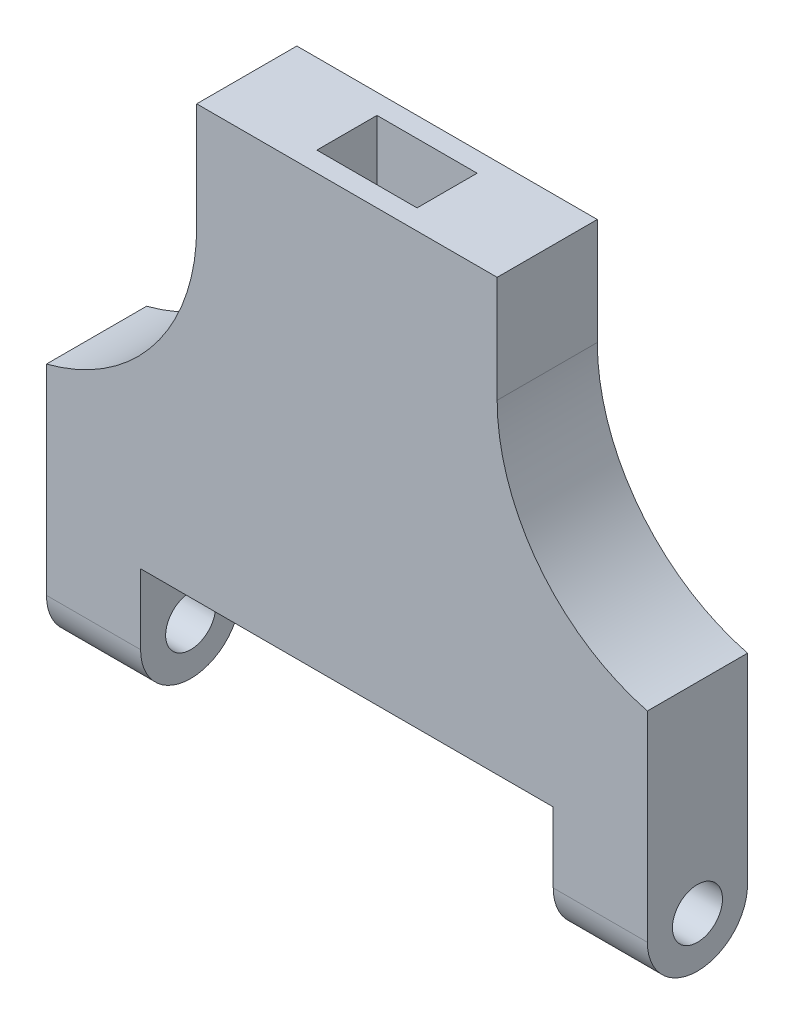
SolidWorks part; units mm, degrees
ref_plane "Front" through (0, 0, 0) normal (0, 0, 1) x (1, 0, 0)
ref_plane "Top" through (0, 0, 0) normal (0, 1, 0) x (1, 0, 0)
ref_plane "Right" through (0, 0, 0) normal (1, 0, 0) x (0, 0, -1)
sketch "Sketch1" plane through (0, 0, 0) normal (0, 0, 1) x (1, 0, 0)
  line L1 (0, 0) -> (20, 0)
  line L2 (0, 0) -> (0, 60)
  line L3 (0, 60) -> (20, 60)
  line L4 (20, 0) -> (20, 60)
  dimension "D1" = 60
  dimension "D2" = 20
extrude "Boss-Extrude1" add sketch "Sketch1" along normal blind 5
sketch "Sketch2" plane through (20, 0, 0) normal (1, 0, 0) x (0, 0, -1)
  line L0 (-5, 60) -> (0, 60) construction
  circle A0 centre (-2.5, 60) radius 2.5
  circle A1 centre (-2.5, 60) radius 1.25
  dimension "D1" = 2.5
extrude "Boss-Extrude2" add sketch "Sketch2" against normal up to surface (20 mm away) up to face at (0, 30, 2.5)
sketch "Sketch3" plane through (0, 0, 0) normal (-1, 0, 0) x (0, 0, 1)
  line L0 (3.75, 60) -> (1.25, 60) construction
  circle A0 centre (2.5, 60) radius 1.25
extrude "Cut-Extrude1" cut sketch "Sketch3" against normal blind 29
sketch "Sketch4" plane through (0, 0, 0) normal (-1, 0, 0) x (0, 0, 1)
  line L0 (5, 0) -> (0, 0) construction
  circle A0 centre (2.5, 0) radius 2.5
  circle A1 centre (2.5, 0) radius 1.25
  dimension "D1" = 2.5
extrude "Boss-Extrude3" add sketch "Sketch4" against normal up to surface (20 mm away) up to face at (20, 30.625, 2.5)
sketch "Sketch5" plane through (20, 0, 0) normal (1, 0, 0) x (0, 0, -1)
  line L0 (-3.75, 0) -> (-1.25, 0) construction
  circle A0 centre (-2.5, 0) radius 1.25
extrude "Cut-Extrude2" cut sketch "Sketch5" against normal blind 29
sketch "Sketch6" plane through (0, 0, 0) normal (-1, 0, 0) x (0, 0, 1)
  line L2 (5, 60) -> (5, 70)
  line L3 (5, 70) -> (0, 70)
  line L4 (0, 60) -> (0, 70)
  circle A0 centre (2.5, 60) radius 1.25
  arc A1 (0, 60) -> (5, 60) centre (2.5, 60) ccw
  dimension "D1" = 10
extrude "Boss-Extrude4" add sketch "Sketch6" along normal blind 30
sketch "Sketch7" plane through (0, 0, 0) normal (0, 0, -1) x (-1, 0, 0)
  line L1 (4.7, 63.5) -> (25.3, 63.5)
  line L2 (4.7, 63.5) -> (4.7, 56.5)
  line L3 (4.7, 56.5) -> (25.3, 56.5)
  line L4 (25.3, 63.5) -> (25.3, 56.5)
  line L6 (30, 70) -> (0, 70) construction
  point P4 (25.3, 60)
  point P5 (15, 63.5)
  point P9 (15, 70)
  dimension "D1" = 20.6
  dimension "D2" = 7
extrude "Cut-Extrude3" cut sketch "Sketch7" against normal blind 30
sketch "Sketch8" plane through (0, 0, 0) normal (-1, 0, 0) x (0, 0, 1)
  line L1 (-28.189, 70.3602) -> (32.3225, 70.3602)
  line L2 (-28.189, 70.3602) -> (-28.189, -8.2037)
  line L3 (-28.189, -8.2037) -> (32.3225, -8.2037)
  line L4 (32.3225, 70.3602) -> (32.3225, -8.2037)
extrude "Cut-Extrude4" cut sketch "Sketch8" against normal blind 41
sketch "Sketch13" plane through (0, 0, 0) normal (0, 0, -1) x (-1, 0, 0)
  line L0 (30, 70) -> (0, 70) construction
  line L1 (22.5, 70) -> (7.5, 70)
  line L2 (22.5, 70) -> (22.5, 85)
  line L3 (22.5, 85) -> (7.5, 85)
  line L4 (7.5, 70) -> (7.5, 85)
  point P6 (15, 85)
  point P7 (15, 70)
  dimension "D1" = 15
  dimension "D2" = 15
extrude "Boss-Extrude6" add sketch "Sketch13" against normal up to surface (5 mm away) up to face at (-15, 63.375, 5)
fillet "Fillet1" radius 10 2 edges at (-22.5, 70, 2.5) (-7.5, 70, 2.5)
sketch "Sketch14" plane through (0, 85, 0) normal (0, 1, 0) x (1, 0, 0)
  line L0 (-7.5, -5) -> (-22.5, -5) construction
  line L1 (-12.5, -4) -> (-17.5, -4)
  line L2 (-12.5, -4) -> (-12.5, -1)
  line L3 (-12.5, -1) -> (-17.5, -1)
  line L4 (-17.5, -4) -> (-17.5, -1)
  line L5 (-7.5, -5) -> (-7.5, 0) construction
  point P4 (-15, -4)
  point P7 (-15, -5)
  point P8 (-12.5, -2.5)
  point P11 (-7.5, -2.5)
  dimension "D1" = 3
  dimension "D2" = 5
extrude "Cut-Extrude6" cut sketch "Sketch14" against normal blind 14
